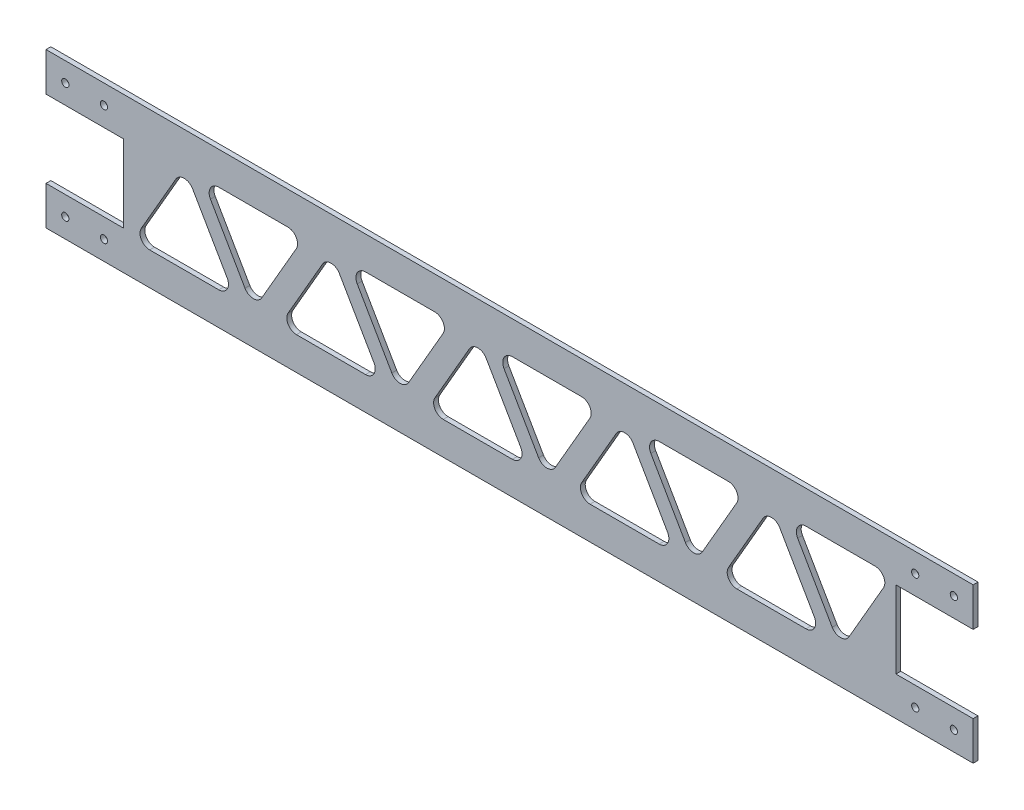
SolidWorks part; units mm, degrees
material "6063-T1"
ref_plane "Front Plane" through (0, 0, 0) normal (0, 0, 1) x (1, 0, 0)
ref_plane "Top Plane" through (0, 0, 0) normal (0, 1, 0) x (1, 0, 0)
ref_plane "Right Plane" through (0, 0, 0) normal (1, 0, 0) x (0, 0, -1)
sketch "Sketch1" plane through (0, 0, 0) normal (0, 0, 1) x (1, 0, 0)
  line L1 (-304.8, 50.8) -> (304.8, 50.8)
  line L2 (-304.8, 50.8) -> (-304.8, -50.8)
  line L3 (-304.8, -50.8) -> (304.8, -50.8)
  line L4 (304.8, 50.8) -> (304.8, -50.8)
  line L5 (-304.8, 50.8) -> (304.8, -50.8) construction
  line L6 (-304.8, -50.8) -> (304.8, 50.8) construction
  point P0 (0, 0)
  dimension "D1" = 609.6
  dimension "D2" = 101.6
extrude "Boss-Extrude1" add sketch "Sketch1" along normal blind 3.175
sketch "Sketch2" plane through (0, 0, 3.175) normal (0, 0, 1) x (1, 0, 0)
  line L0 (-304.8, 50.8) -> (-304.8, -50.8) construction
  line L1 (-304.8, -50.8) -> (304.8, -50.8) construction
  line L2 (304.8, 50.8) -> (-304.8, 50.8) construction
  line L3 (0, 50.8) -> (0, -50.8) construction
  circle A0 centre (-292.1, 38.1) radius 2.3813
  circle A1 centre (-292.1, -38.1) radius 2.3813
  circle A2 centre (-266.7, 38.1) radius 2.3813
  circle A3 centre (-266.7, -38.1) radius 2.3813
  circle A4 centre (-292.1, -19.05) radius 2.3813
  circle A5 centre (-266.7, -19.05) radius 2.3813
  circle A6 centre (266.7, -19.05) radius 2.3813
  circle A7 centre (292.1, -19.05) radius 2.3813
  circle A8 centre (266.7, -38.1) radius 2.3813
  circle A9 centre (266.7, 38.1) radius 2.3813
  circle A10 centre (292.1, -38.1) radius 2.3813
  circle A11 centre (292.1, 38.1) radius 2.3813
  dimension "D9" = 4.7625
  dimension "D10" = 4.7625
  dimension "D11" = 4.7625
  dimension "D12" = 4.7625
  dimension "D13" = 4.7625
  dimension "D14" = 4.7625
  dimension "D1" = 12.7
  dimension "D2" = 25.4
  dimension "D3" = 12.7
  dimension "D4" = 38.1
  dimension "D5" = 12.7
  dimension "D6" = 12.7
  dimension "D7" = 12.7
  dimension "D8" = 12.7
  dimension "D15" = 12.7
  dimension "D16" = 19.05
  dimension "D17" = 19.05
extrude "Cut-Extrude1" cut sketch "Sketch2" against normal through all
sketch "Sketch3" plane through (0, 0, 3.175) normal (0, 0, 1) x (1, 0, 0)
  line L0 (-304.8, -50.8) -> (304.8, -50.8) construction
  line L1 (-185.6917, -19.685) -> (-208.4219, 19.685)
  line L2 (-219.4205, 19.685) -> (-242.1507, -19.685)
  line L3 (-236.6515, -29.21) -> (-191.1909, -29.21)
  line L4 (304.8, 50.8) -> (-304.8, 50.8) construction
  line L5 (-304.8, 50.8) -> (-304.8, -50.8) construction
  line L6 (-162.9614, -19.685) -> (-140.2311, 19.685)
  line L7 (-145.7304, 29.21) -> (-191.1909, 29.21)
  line L8 (-196.6902, 19.685) -> (-173.9599, -19.685)
  line L45 (-66.4414, -19.685) -> (-43.7111, 19.685)
  line L46 (-100.1702, 19.685) -> (-77.4399, -19.685)
  line L47 (-49.2104, 29.21) -> (-94.6709, 29.21)
  line L48 (-140.1315, -29.21) -> (-94.6709, -29.21)
  line L49 (-89.1717, -19.685) -> (-111.9019, 19.685)
  line L50 (-122.9005, 19.685) -> (-145.6307, -19.685)
  line L51 (30.0786, -19.685) -> (52.8089, 19.685)
  line L52 (-3.6502, 19.685) -> (19.0801, -19.685)
  line L53 (47.3096, 29.21) -> (1.8491, 29.21)
  line L54 (-43.6115, -29.21) -> (1.8491, -29.21)
  line L55 (7.3483, -19.685) -> (-15.3819, 19.685)
  line L56 (-26.3805, 19.685) -> (-49.1107, -19.685)
  line L57 (126.5986, -19.685) -> (149.3289, 19.685)
  line L58 (92.8698, 19.685) -> (115.6001, -19.685)
  line L59 (143.8296, 29.21) -> (98.3691, 29.21)
  line L60 (52.9085, -29.21) -> (98.3691, -29.21)
  line L61 (103.8683, -19.685) -> (81.1381, 19.685)
  line L62 (70.1395, 19.685) -> (47.4093, -19.685)
  line L63 (223.1186, -19.685) -> (245.8489, 19.685)
  line L64 (189.3898, 19.685) -> (212.1201, -19.685)
  line L65 (240.3496, 29.21) -> (194.8891, 29.21)
  line L66 (149.4285, -29.21) -> (194.8891, -29.21)
  line L67 (200.3883, -19.685) -> (177.6581, 19.685)
  line L68 (166.6595, 19.685) -> (143.9293, -19.685)
  circle A0 centre (-213.9212, -9.7367) radius 19.4733 construction
  circle A1 centre (-168.4606, 9.7367) radius 19.4733 construction
  arc A2 (-66.4414, -19.685) -> (-77.4399, -19.685) centre (-71.9406, -16.51) cw
  arc A3 (-94.6709, 29.21) -> (-100.1702, 19.685) centre (-94.6709, 22.86) ccw
  arc A4 (-43.7111, 19.685) -> (-49.2104, 29.21) centre (-49.2104, 22.86) ccw
  arc A5 (-89.1717, -19.685) -> (-94.6709, -29.21) centre (-94.6709, -22.86) cw
  arc A6 (-111.9019, 19.685) -> (-122.9005, 19.685) centre (-117.4012, 16.51) ccw
  arc A7 (-145.6307, -19.685) -> (-140.1315, -29.21) centre (-140.1315, -22.86) ccw
  arc A8 (30.0786, -19.685) -> (19.0801, -19.685) centre (24.5794, -16.51) cw
  arc A9 (1.8491, 29.21) -> (-3.6502, 19.685) centre (1.8491, 22.86) ccw
  arc A10 (-191.1909, 29.21) -> (-196.6902, 19.685) centre (-191.1909, 22.86) ccw
  arc A11 (-140.2311, 19.685) -> (-145.7304, 29.21) centre (-145.7304, 22.86) ccw
  arc A12 (-162.9614, -19.685) -> (-173.9599, -19.685) centre (-168.4606, -16.51) cw
  arc A13 (-185.6917, -19.685) -> (-191.1909, -29.21) centre (-191.1909, -22.86) cw
  arc A14 (-208.4219, 19.685) -> (-219.4205, 19.685) centre (-213.9212, 16.51) ccw
  arc A15 (-242.1507, -19.685) -> (-236.6515, -29.21) centre (-236.6515, -22.86) ccw
  arc A16 (52.8089, 19.685) -> (47.3096, 29.21) centre (47.3096, 22.86) ccw
  arc A17 (7.3483, -19.685) -> (1.8491, -29.21) centre (1.8491, -22.86) cw
  arc A18 (-15.3819, 19.685) -> (-26.3805, 19.685) centre (-20.8812, 16.51) ccw
  arc A19 (-49.1107, -19.685) -> (-43.6115, -29.21) centre (-43.6115, -22.86) ccw
  arc A20 (126.5986, -19.685) -> (115.6001, -19.685) centre (121.0994, -16.51) cw
  arc A21 (98.3691, 29.21) -> (92.8698, 19.685) centre (98.3691, 22.86) ccw
  arc A22 (149.3289, 19.685) -> (143.8296, 29.21) centre (143.8296, 22.86) ccw
  arc A23 (103.8683, -19.685) -> (98.3691, -29.21) centre (98.3691, -22.86) cw
  arc A24 (81.1381, 19.685) -> (70.1395, 19.685) centre (75.6388, 16.51) ccw
  arc A25 (47.4093, -19.685) -> (52.9085, -29.21) centre (52.9085, -22.86) ccw
  arc A26 (223.1186, -19.685) -> (212.1201, -19.685) centre (217.6194, -16.51) cw
  arc A27 (194.8891, 29.21) -> (189.3898, 19.685) centre (194.8891, 22.86) ccw
  arc A28 (245.8489, 19.685) -> (240.3496, 29.21) centre (240.3496, 22.86) ccw
  arc A29 (200.3883, -19.685) -> (194.8891, -29.21) centre (194.8891, -22.86) cw
  arc A30 (177.6581, 19.685) -> (166.6595, 19.685) centre (172.1588, 16.51) ccw
  arc A31 (143.9293, -19.685) -> (149.4285, -29.21) centre (149.4285, -22.86) ccw
  point P62 (-168.4606, -29.21)
  point P67 (-213.9212, 29.21)
  point P70 (-247.65, -29.21)
  dimension "D8" = 6.35
  dimension "D1" = 21.59
  dimension "D2" = 21.59
  dimension "D3" = 21.59
  dimension "D4" = 21.59
  dimension "D5" = 10.16
  dimension "D6" = 57.15
  dimension "D7" = 5
extrude "Cut-Extrude2" cut sketch "Sketch3" against normal through all
fillet "Fillet1" [suppressed] radius 5.08
sketch "Sketch4" plane through (0, 0, 3.175) normal (0, 0, 1) x (1, 0, 0)
  line L0 (-304.8, 50.8) -> (-304.8, -50.8) construction
  line L1 (-304.8, 25.4) -> (-254, 25.4)
  line L2 (-304.8, 25.4) -> (-304.8, -25.4)
  line L3 (-304.8, -25.4) -> (-254, -25.4)
  line L4 (-254, 25.4) -> (-254, -25.4)
  line L5 (304.8, 50.8) -> (-304.8, 50.8) construction
  line L6 (-304.8, -50.8) -> (304.8, -50.8) construction
  line L7 (304.8, -50.8) -> (304.8, 50.8) construction
  line L8 (304.8, 25.4) -> (254, 25.4)
  line L9 (304.8, 25.4) -> (304.8, -25.4)
  line L10 (304.8, -25.4) -> (254, -25.4)
  line L11 (254, 25.4) -> (254, -25.4)
  dimension "D1" = 50.8
  dimension "D2" = 25.4
  dimension "D3" = 25.4
  dimension "D4" = 50.8
  dimension "D5" = 25.4
  dimension "D6" = 50.8
extrude "Cut-Extrude3" cut sketch "Sketch4" against normal through all
